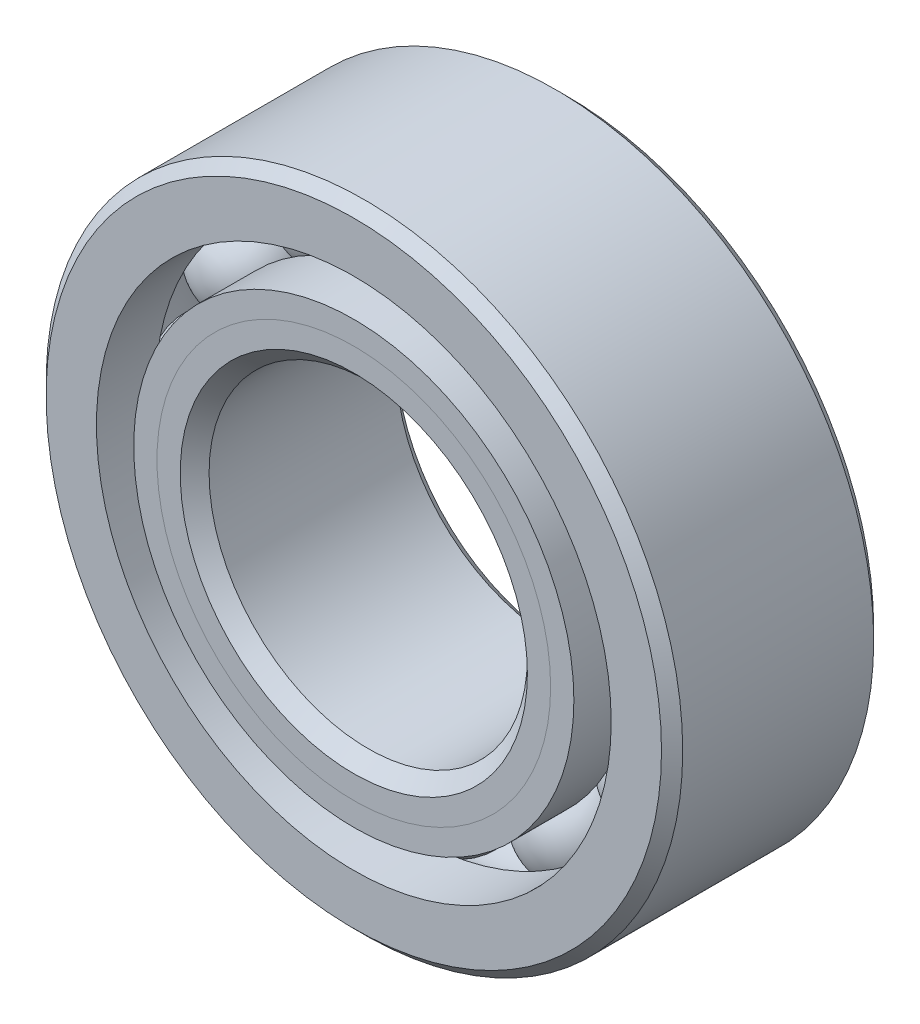
SolidWorks part; units mm, degrees
ref_plane "Front Plane" through (0, 0, 0) normal (0, 0, 1) x (1, 0, 0)
ref_plane "Top Plane" through (0, 0, 0) normal (0, 1, 0) x (1, 0, 0)
ref_plane "Right Plane" through (0, 0, 0) normal (1, 0, 0) x (0, 0, -1)
sketch "Sketch1" plane through (0, 0, 0) normal (1, 0, 0) x (0, 0, -1)
  line L0 (-1.5875, 0) -> (1.5875, 0) construction
  line L1 (0, 4.7625) -> (0, -4.7625) construction
  line L2 (1.4288, 4.7625) -> (-1.4288, 4.7625)
  line L3 (-1.4288, 4.7625) -> (-1.5875, 4.6037)
  line L4 (-1.5875, 4.6037) -> (-1.5875, 3.851)
  line L5 (-1.5875, 3.851) -> (-0.7056, 3.851)
  line L6 (1.5875, 3.851) -> (0.7056, 3.851)
  line L7 (1.5875, 4.6037) -> (1.5875, 3.851)
  line L8 (1.4288, 4.7625) -> (1.5875, 4.6037)
  line L9 (0, 4.7625) -> (0, 3.5719) construction
  line L10 (0, 3.5719) -> (0, 2.3813) construction
  arc A0 (-0.7056, 3.851) -> (0.7056, 3.851) centre (0, 3.5719) cw
  point P14 (0, 2.3813)
  dimension "Width" = 3.175
  dimension "OD" = 9.525
  dimension "D1" = 45
  dimension "D2" = 0.1588
  dimension "D3" = 1.4111
  dimension "D4" = 0.2791
revolve "Revolve1" add sketch "Sketch1" angle 360 about L0
sketch "Sketch2" plane through (0, 0, 0) normal (1, 0, 0) x (0, 0, -1)
  line L0 (-1.5875, 3.2928) -> (-0.7056, 3.2928)
  line L1 (-1.5875, 4.6037) -> (-1.5875, -4.6037) construction
  line L2 (-1.5875, 3.2928) -> (-1.5875, 2.945)
  line L3 (-1.5875, 2.945) -> (-1.2397, 2.5972)
  line L4 (-1.2397, 2.5972) -> (0, 2.5972)
  line L5 (0, 4.7625) -> (0, -4.7625) construction
  line L6 (0, 2.5972) -> (0, 2.8131)
  line L7 (0, 2.8131) -> (0, 2.3813) construction
  line L8 (-1.5875, 3.2928) -> (-1.5875, 2.5972) construction
  line L9 (-1.5875, 2.5972) -> (-1.2397, 2.5972) construction
  arc A0 (-0.7056, 3.2928) -> (0, 2.8131) centre (0, 3.5719) ccw
  arc A1 (0.7056, 3.851) -> (-0.7056, 3.851) centre (0, 3.5719) ccw construction
  circle A2 centre (0, 3.5719) radius 0.7588 construction
  dimension "D1" = 45
revolve "Revolve2" add sketch "Sketch2" angle 360 about L0
sketch "Sketch3" plane through (0, 0, 0) normal (1, 0, 0) x (0, 0, -1)
  line L0 (-1.5875, 2.945) -> (-1.2397, 2.5972)
  line L1 (-1.2397, 2.5972) -> (0, 2.5972)
  line L2 (0, 2.5972) -> (0, 2.8131)
  line L3 (-1.5875, 2.945) -> (-1.5875, 2.5972)
  line L4 (-1.5875, 3.2928) -> (-1.5875, 2.5972) construction
  line L5 (-1.5875, 2.5972) -> (-1.3716, 2.3813)
  line L6 (-1.3716, 2.3813) -> (1.4288, 2.3812)
  line L7 (1.4288, 4.7625) -> (1.4288, -4.7625) construction
  line L8 (1.4288, 2.3812) -> (1.5875, 2.54)
  line L9 (1.5875, -4.6037) -> (1.5875, 4.6037) construction
  line L10 (1.5875, 2.54) -> (1.5875, 3.2928)
  line L11 (1.5875, 3.2928) -> (0.7056, 3.2928)
  line L13 (1.4288, 4.7625) -> (1.5875, 4.6037) construction
  circle A0 centre (0, 3.5719) radius 0.7588 construction
  arc A1 (0.7056, 3.2928) -> (0, 2.8131) centre (0, 3.5719) cw
revolve "Revolve3" add sketch "Sketch3" angle 360 about L0
sketch "Sketch4" plane through (0, 0, 0) normal (1, 0, 0) x (0, 0, -1)
  line L0 (-0.7588, 3.5719) -> (0.7588, 3.5719)
  circle A1 centre (0, 3.5719) radius 0.7588 construction
  arc A2 (-0.7588, 3.5719) -> (0.7588, 3.5719) centre (0, 3.5719) cw
  arc A3 (0.7056, 3.851) -> (-0.7056, 3.851) centre (0, 3.5719) ccw construction
revolve "Revolve4" add sketch "Sketch4" angle 360 about L0
ref_axis "Axis1" through (0, 0, -1.5875) along (0, 0, 1)
pattern_circular "CirPattern1" count 12 every 30 about axis through (0, 0, -1.5875) along (0, 0, 1) of bodies 104
equation "\"D2@Sketch1\" = \"Width@Sketch1\"*.05"
equation "\"D3@Sketch1\" = \"Width@Sketch1\"/2.25"
equation "\"D4@Sketch1\" = (((\"OD@Sketch1\"-\"Width@Sketch1\")/2)/3.25)/3.5"
equation "\"D2@CirPattern1\" = 360/\"Balls@CirPattern1\""
